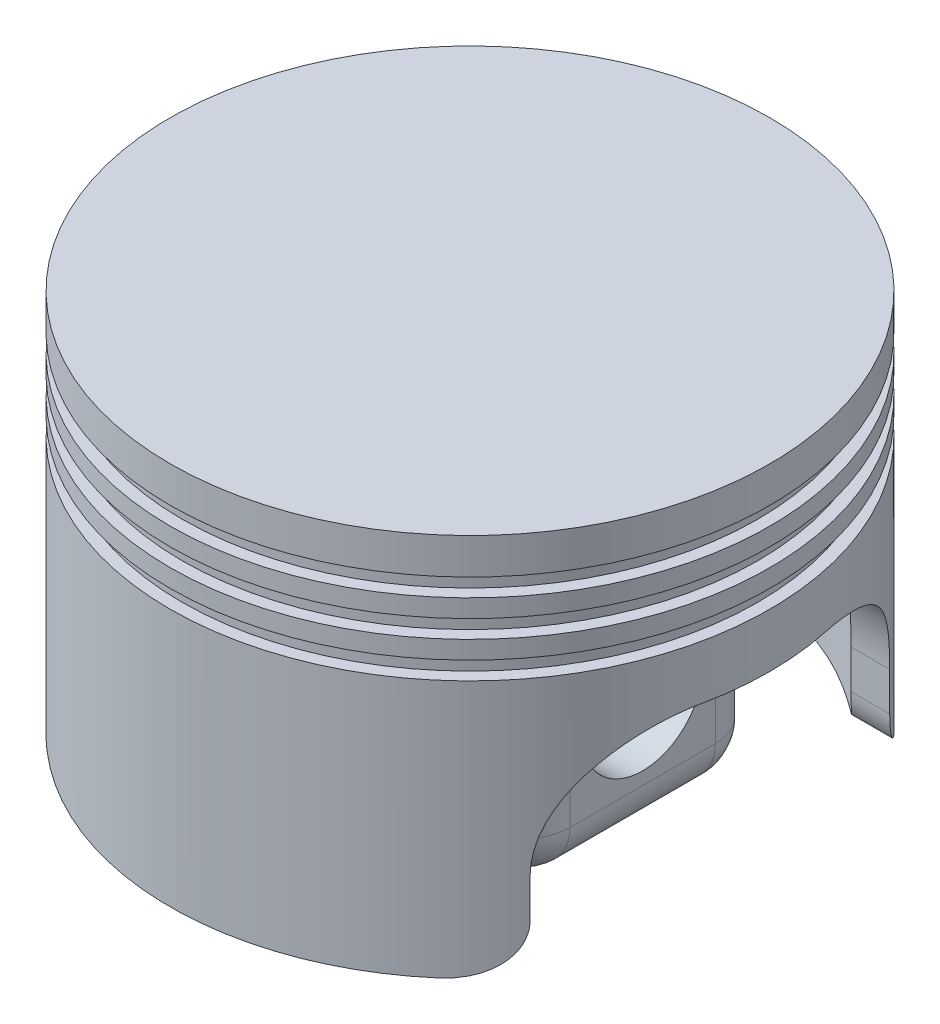
SolidWorks part; units mm, degrees
ref_plane "Front Plane" through (0, 0, 0) normal (0, 0, 1) x (1, 0, 0)
ref_plane "Top Plane" through (0, 0, 0) normal (0, 1, 0) x (1, 0, 0)
ref_plane "Right Plane" through (0, 0, 0) normal (1, 0, 0) x (0, 0, -1)
sketch "Schizzo1" plane through (0, 0, 0) normal (0, 0, 1) x (1, 0, 0)
  line L0 (0, 0) -> (63.5, 0)
  line L1 (34.925, 0) -> (-34.925, 0) construction
  line L2 (63.5, -81.28) -> (57.15, -81.28)
  line L3 (57.15, -81.28) -> (57.15, -19)
  line L4 (57.15, -19) -> (0, -19)
  line L5 (0, -89.408) -> (0, 89.408) construction
  line L6 (0, -19) -> (0, 0)
  line L7 (63.5, 0) -> (63.5, -81.28)
  dimension "D1" = 63.5
  dimension "D2" = 81.28
  dimension "D3" = 19
  dimension "D4" = 6.35
revolve "Rivoluzione3" add sketch "Schizzo1" angle 360 about L6
sketch "Schizzo2" plane through (0, 0, 0) normal (0, 0, 1) x (1, 0, 0)
  line L0 (60.96, -7.62) -> (63.5, -7.62)
  line L1 (63.5, -7.62) -> (63.5, -11.43)
  line L2 (63.5, -11.43) -> (60.96, -11.43)
  line L3 (60.96, -11.43) -> (60.96, -7.62)
  line L4 (69.85, 0) -> (-69.85, 0) construction
  dimension "D1" = 7.62
  dimension "D2" = 3.81
  dimension "D3" = 2.54
  dimension "D4" = 63.5
ref_axis "Assi1" through (0, -133.4196, 0) along (0, 1, 0)
revolve "Taglia-Rivoluzione1" cut sketch "Schizzo2" angle 360 about axis through (0, -133.4196, 0) along (0, 1, 0)
pattern_linear "Ripetizione a L1" count 3 spacing 7.62 along (0, -1, 0) of "Taglia-Rivoluzione1"
sketch "Schizzo6" plane through (0, 0, 0) normal (1, 0, 0) x (0, 0, -1)
  line L0 (0, 44.704) -> (0, -44.704) construction
  line L1 (-38.1, -38.1) -> (38.1, -38.1)
  line L2 (-38.1, -38.1) -> (-38.1, -81.28)
  line L3 (-38.1, -81.28) -> (38.1, -81.28)
  line L4 (38.1, -38.1) -> (38.1, -81.28)
  line L5 (-38.1, -38.1) -> (38.1, -81.28) construction
  line L6 (-38.1, -81.28) -> (38.1, -38.1) construction
  line L7 (-57.15, -81.28) -> (57.15, -81.28) construction
  line L9 (69.85, 0) -> (-69.85, 0) construction
  point P0 (0, -59.69)
  dimension "D1" = 76.2
  dimension "D2" = 38.1
extrude "Taglio-Estrusione1" cut sketch "Schizzo6" against normal mid plane 252
fillet "Raccordo1" radius 25 4 edges at (-46.6985, -38.1, 38.1) (46.6985, -38.1, 38.1) (46.6985, -38.1, -38.1) (-46.6985, -38.1, -38.1)
fillet "Raccordo2" radius 10 4 edges at (46.6985, -81.28, -38.1) (-46.6985, -81.28, -38.1) (46.6985, -81.28, 38.1) (-46.6985, -81.28, 38.1)
sketch "Schizzo8" plane through (0, -19, 0) normal (0, -1, 0) x (1, 0, 0)
  line L0 (-27.05, 0) -> (0, 0) construction
  line L1 (-36.55, 25.4) -> (-17.55, 25.4)
  line L2 (-36.55, 25.4) -> (-36.55, -25.4)
  line L3 (-36.55, -25.4) -> (-17.55, -25.4)
  line L4 (-17.55, 25.4) -> (-17.55, -25.4)
  line L5 (-36.55, 25.4) -> (-17.55, -25.4) construction
  line L6 (-36.55, -25.4) -> (-17.55, 25.4) construction
  point P0 (-27.05, 0)
  dimension "D1" = 19
  dimension "D2" = 50.8
  dimension "D3" = 17.55
extrude "Estrusione-Estrusione1" add sketch "Schizzo8" along normal blind 63.5
mirror "Specchia1" about plane through (0, 0, 0) normal (1, 0, 0) of "Estrusione-Estrusione1"
fillet "Raccordo3" radius 10 4 edges at (-27.05, -82.5, -25.4) (27.05, -82.5, -25.4) (27.05, -82.5, 25.4) (-27.05, -82.5, 25.4)
fillet "Raccordo9" radius 10 10 edges at (-17.55, -45.75, -25.4) (-17.55, -79.5711, -22.4711) (-17.55, -45.75, 25.4) (-17.55, -79.5711, 22.4711) (-17.55, -82.5, 0) (36.55, -45.75, 25.4) (36.55, -79.5711, 22.4711) (36.55, -45.75, -25.4) (36.55, -79.5711, -22.4711) (36.55, -82.5, 0)
fillet "Raccordo10" radius 10 10 edges at (17.55, -45.75, -25.4) (17.55, -79.5711, -22.4711) (17.55, -45.75, 25.4) (17.55, -79.5711, 22.4711) (17.55, -82.5, 0) (-36.55, -45.75, 25.4) (-36.55, -79.5711, 22.4711) (-36.55, -45.75, -25.4) (-36.55, -79.5711, -22.4711) (-36.55, -82.5, 0)
sketch "Schizzo11" plane through (-36.55, 0, 0) normal (-1, 0, 0) x (0, 0, 1)
  line L0 (0, -133.4196) -> (0, 71.5395) construction
  line L1 (-15.4, -82.5) -> (15.4, -82.5) construction
  circle A0 centre (0, -57.1) radius 12.7
  dimension "D1" = 25.4
  dimension "D2" = 25.4
extrude "Taglio-Estrusione2" cut sketch "Schizzo11" against normal through all
fillet "Raccordo11" radius 5 1 edges at (0, -19, -57.15)
